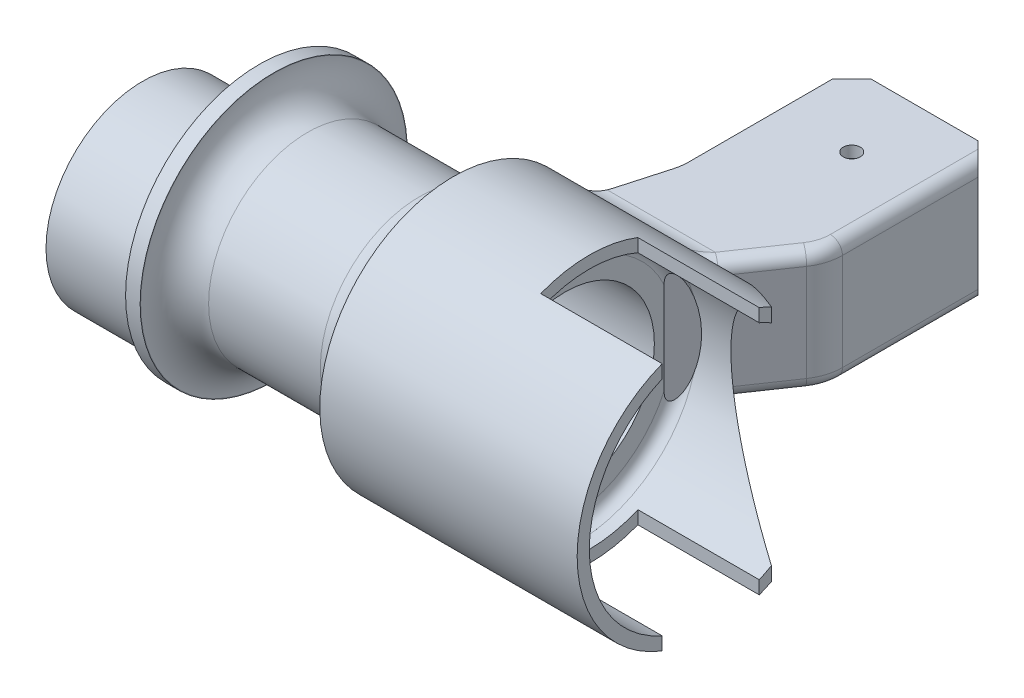
SolidWorks part; units mm, degrees
ref_plane "Alzado" through (0, 0, 0) normal (0, 0, 1) x (1, 0, 0)
ref_plane "Planta" through (0, 0, 0) normal (0, 1, 0) x (1, 0, 0)
ref_plane "Vista lateral" through (0, 0, 0) normal (1, 0, 0) x (0, 0, -1)
sketch "Croquis1" plane through (0, 0, 0) normal (1, 0, 0) x (0, 0, -1)
  circle A0 centre (0, 0) radius 18.4
  circle A1 centre (0, 0) radius 20.4
  dimension "D1" = 36.8
  dimension "D2" = 2
extrude "Saliente-Extruir1" add sketch "Croquis1" along normal blind 60
sketch "Croquis2" plane through (0, 0, 0) normal (-1, 0, 0) x (0, 0, 1)
  line L0 (10.1074, 15.3753) -> (-3.8452, -5.8493) construction
  line L1 (0, 0) -> (0.8977, 15.474) construction
  line L2 (0.8977, 15.474) -> (13.8497, 6.9596) construction
  line L3 (13.8497, 6.9596) -> (12.952, -8.5144) construction
  line L4 (12.952, -8.5144) -> (-0.8977, -15.474) construction
  line L5 (-0.8977, -15.474) -> (-13.8497, -6.9596) construction
  line L6 (-13.8497, -6.9596) -> (-12.952, 8.5144) construction
  line L7 (-12.952, 8.5144) -> (0.8977, 15.474) construction
  line L8 (-12.952, 8.5144) -> (0, 0) construction
  line L9 (0, 0) -> (13.8497, 6.9596) construction
  line L10 (12.952, -8.5144) -> (0, 0) construction
  line L11 (0, 0) -> (-13.8497, -6.9596) construction
  line L12 (-0.8977, -15.474) -> (0, 0) construction
  line L13 (6.9883, -0.4054) -> (13.4009, -0.7774) construction
  line L20 (0, 0) -> (0, -32.026) construction
  circle A8 centre (0.8977, 15.474) radius 1.5
  circle A9 centre (-12.952, 8.5144) radius 1.5
  circle A13 centre (-13.8497, -6.9596) radius 1.5
  circle A14 centre (0, 0) radius 27.5
  arc A15 (9.7768, 9.1979) -> (8.6476, -10.2668) centre (0, 0) ccw
  circle A16 centre (6.9883, -0.4054) radius 6.4234
  arc A17 (9.7768, 9.1979) -> (8.6476, -10.2668) centre (6.9883, -0.4054) ccw
  dimension "D1" = 60
  dimension "D2" = 6.4234
  dimension "D3" = 25.4
  dimension "D4" = 3
  dimension "D9" = 7
  dimension "D10" = 55
  dimension "D11" = 20
  dimension "D5" = 60
  dimension "D6" = 60
  dimension "D7" = 60
  dimension "D8" = 60
extrude "Saliente-Extruir2" add sketch "Croquis2" along normal blind 3
sketch "Croquis15" plane through (-3, 0, 0) normal (-1, 0, 0) x (0, 0, 1)
  line L0 (21.3883, -0.4054) -> (26.3883, -0.4054) construction
  line L1 (6.9883, 18.9946) -> (6.9883, 13.9946)
  line L2 (6.9883, -14.8054) -> (6.9883, -19.8054)
  arc A0 (6.9883, -14.8054) -> (6.9883, 13.9946) centre (6.9883, -0.4054) ccw
  arc A1 (6.9883, -19.8054) -> (6.9883, 18.9946) centre (6.9883, -0.4054) ccw
  dimension "D1" = 28.8
  dimension "D2" = 5
extrude "Saliente-Extruir5" add sketch "Croquis15" along normal blind 10
sketch "Croquis16" plane through (-3, 0, 0) normal (-1, 0, 0) x (0, 0, 1)
  circle A0 centre (6.9883, -0.4054) radius 19.9
  circle A1 centre (6.9883, -0.4054) radius 14.4
  dimension "D1" = 39.8
extrude "Saliente-Extruir6" add sketch "Croquis16" along normal blind 17
sketch "Croquis17" plane through (-3, 0, 0) normal (1, 0, 0) x (0, 0, -1)
  circle A0 centre (-6.9883, -0.4054) radius 13
  circle A1 centre (-6.9883, -0.4054) radius 15
  dimension "D1" = 26
  dimension "D2" = 30
extrude "Saliente-Extruir7" add sketch "Croquis17" against normal blind 2
sketch "Croquis9" plane through (0, 0, 0) normal (0, -1, 0) x (1, 0, 0)
  line L0 (73.6502, -40.4) -> (73.6502, -75.4)
  line L1 (73.6502, -75.4) -> (43.6502, -75.4)
  line L2 (43.6502, -75.4) -> (43.6502, -40.4)
  line L5 (73.6502, -40.4) -> (60, -20.4)
  line L6 (0, -20.4) -> (60, -20.4) construction
  line L7 (60, -20.4) -> (38, -20.4)
  line L8 (38, -20.4) -> (43.6502, -40.4)
  line L9 (58.6502, -75.4) -> (58.6502, -60.4) construction
  line L11 (60, -20.4) -> (60, -17.9747) construction
  line L12 (60, -20.4) -> (60, 20.4) construction
  circle A1 centre (58.6502, -60.4) radius 1.75
  dimension "D6" = 15
  dimension "D5" = 3.5
  dimension "D1" = 35
  dimension "D2" = 30
  dimension "D3" = 20
  dimension "D4" = 22
extrude "Saliente-Extruir3" add sketch "Croquis9" along normal mid plane 25 separate body
fillet "Redondeo3" radius 10 2 edges at (43.6502, 0, -40.4) (73.6502, 0, -40.4)
ref_plane "Plano1" through (37, 0, 0) normal (1, 0, 0) x (0, 0, -1)
sketch "Croquis11" plane through (37, 0, 0) normal (1, 0, 0) x (0, 0, -1)
  circle A1 centre (0, 0) radius 27.5
  circle A2 centre (0, 0) radius 20
  dimension "D1" = 40
  dimension "D2" = 55
extrude "Saliente-Extruir4" add sketch "Croquis11" along normal up to surface (23 mm away) up to face at (60, 0, -20.4)
sketch "Croquis18" plane through (60, 0, 0) normal (1, 0, 0) x (0, 0, -1)
  circle A0 centre (0, 0) radius 27.5
  circle A1 centre (0, 0) radius 25
  dimension "D1" = 55
  dimension "D2" = 50
extrude "Saliente-Extruir8" add sketch "Croquis18" along normal blind 30
fillet "Redondeo4" radius 7 5 edges at (40.0058, 0, -27.5) (50.9758, 12.5, -24.4949) (50.9758, -12.5, -24.4949) (0, 0, -20.4) (37, 0, -20.4)
sketch "Croquis19" plane through (77.7427, 0, -1000) normal (0, 1, 0) x (1, 0, 0)
  line L0 (12.2573, -972.5) -> (12.2573, -987.5)
  line L1 (12.2573, -1027.5) -> (12.2573, -972.5) construction
  line L2 (12.2573, -987.5) -> (-12.7427, -972.5)
  line L3 (12.2573, -972.5) -> (-12.8969, -972.5) construction
  line L4 (-12.7427, -972.5) -> (12.2573, -972.5)
  line L5 (12.2573, -990) -> (-12.7427, -990)
  line L6 (-12.7427, -990) -> (-12.7427, -1010)
  line L7 (-12.7427, -1010) -> (12.2573, -1010)
  line L8 (12.2573, -1010) -> (12.2573, -1000)
  line L9 (12.2573, -1000) -> (12.2573, -990)
  dimension "D1" = 25
  dimension "D2" = 15
  dimension "D3" = 20
extrude "Cortar-Extruir4" cut sketch "Croquis19" against normal through all both and the other way through all
fillet "Redondeo5" radius 2.5 1 edges at (60, 0, 25)
sketch "Croquis20" plane through (0, 0, -75.4) normal (0, 0, -1) x (-1, 0, 0)
  line L0 (-73.6502, 0) -> (-58.6502, 0) construction
  line L1 (-73.6502, -12.5) -> (-73.6502, 12.5) construction
  line L2 (-58.6502, 0) -> (-58.6502, 12.5) construction
  line L3 (-43.6502, 12.5) -> (-73.6502, 12.5) construction
  line L5 (-68.7502, 10.1) -> (-48.5502, 10.1)
  line L6 (-68.7502, 10.1) -> (-68.7502, -10.1)
  line L7 (-68.7502, -10.1) -> (-48.5502, -10.1)
  line L8 (-48.5502, 10.1) -> (-48.5502, -10.1)
  line L9 (-68.7502, 10.1) -> (-48.5502, -10.1) construction
  line L10 (-68.7502, -10.1) -> (-48.5502, 10.1) construction
  dimension "D1" = 20.2
  dimension "D2" = 20.2
extrude "Cortar-Extruir5" cut sketch "Croquis20" against normal blind 30
chamfer "Chaflán1" distance 4 angle 45 2 edges at (73.6502, 0, -75.4) (43.6502, 0, -75.4)
fillet "Redondeo6" radius 2.5 8 edges at (63.2738, 13.3074, -25.1967) (68.7056, 12.5, -33.1553) (73.2052, 12.5, -40.5374) (63.2738, -13.3074, -25.1967) (68.7056, -12.5, -33.1553) (73.2052, -12.5, -40.5374) (73.6502, 12.5, -57.4436) (73.6502, -12.5, -57.4436)
